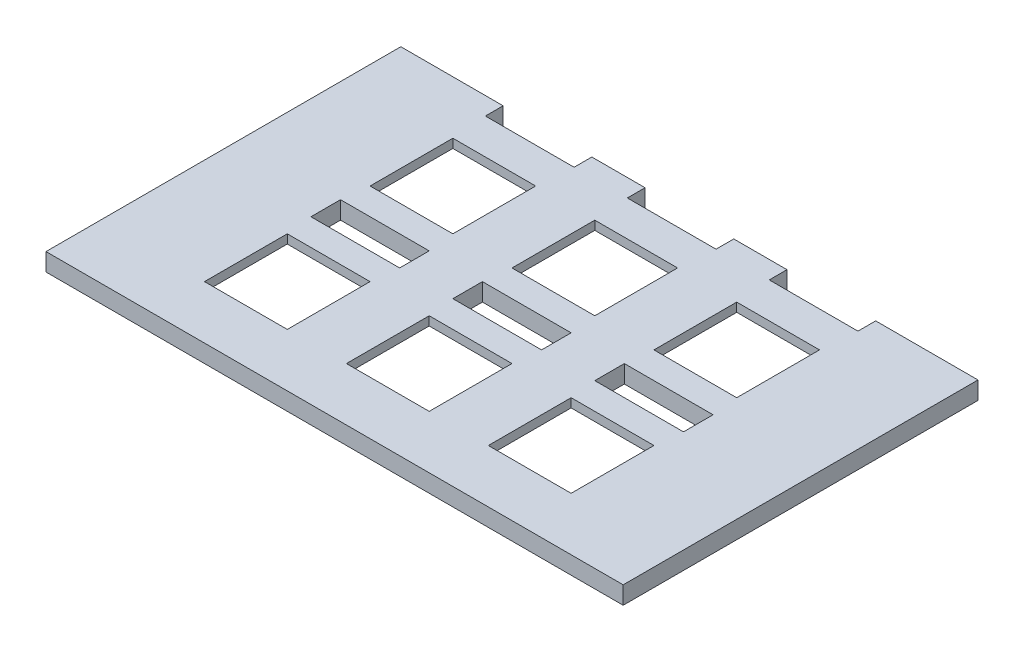
SolidWorks part; units mm, degrees
ref_plane "Front Plane" through (0, 0, 0) normal (0, 0, 1) x (1, 0, 0)
ref_plane "Top Plane" through (0, 0, 0) normal (0, 1, 0) x (1, 0, 0)
ref_plane "Right Plane" through (0, 0, 0) normal (1, 0, 0) x (0, 0, -1)
sketch "Sketch1" plane through (0, 0, 0) normal (0, 1, 0) x (1, 0, 0)
  line L1 (0, 0) -> (87.6, 0)
  line L2 (0, 0) -> (0, 60)
  line L3 (0, 60) -> (87.6, 60)
  line L4 (87.6, 0) -> (87.6, 60)
  dimension "D1" = 87.6
  dimension "D2" = 60
extrude "Boss-Extrude1" add sketch "Sketch1" along normal blind 3
sketch "Sketch2" plane through (87.6, 0, 0) normal (1, 0, 0) x (0, 0, -1)
  line L0 (0, 3) -> (60, 3) construction
  line L1 (2.3, 3) -> (57.7, 3)
  line L2 (2.3, 3) -> (2.3, 0)
  line L3 (2.3, 0) -> (57.7, 0)
  line L4 (57.7, 3) -> (57.7, 0)
  line L5 (0, 0) -> (60, 0) construction
  line L6 (0, 3) -> (0, 0) construction
  line L7 (60, 3) -> (60, 0) construction
  dimension "D1" = 2.3
  dimension "D2" = 2.3
extrude "Boss-Extrude2" add sketch "Sketch2" along normal blind 5
ref_plane "Plane1" through (43.8, 0, 0) normal (1, 0, 0) x (0, 0, -1)
mirror "Mirror2" about plane through (43.8, 0, 0) normal (1, 0, 0) of "Boss-Extrude2"
sketch "Sketch3" plane through (0, 0, 0) normal (0, -1, 0) x (1, 0, 0)
  line L0 (43.8, 0) -> (43.8, -60) construction
  line L1 (0, 0) -> (87.6, 0) construction
  line L2 (87.6, -60) -> (0, -60) construction
  line L3 (-5, -44) -> (90.6, -44) construction
  line L6 (43.8, -30) -> (51.1237, -30) construction
  line L7 (12.8, -51) -> (26.8, -51)
  line L8 (12.8, -51) -> (12.8, -37)
  line L9 (12.8, -37) -> (26.8, -37)
  line L10 (26.8, -51) -> (26.8, -37)
  line L11 (12.8, -51) -> (26.8, -37) construction
  line L12 (12.8, -37) -> (26.8, -51) construction
  line L13 (47.4618, -30) -> (47.4618, -60) construction
  line L14 (47.4618, -30) -> (47.4618, 0) construction
  line L15 (47.4618, -15) -> (43.8, -15) construction
  line L16 (47.4618, -45) -> (43.8, -45) construction
  point P12 (19.8, -44)
  dimension "D1" = 14
  dimension "D2" = 14
  dimension "D3" = 24
  dimension "D4" = 14
ref_plane "Plane2" through (0, 0, -30) normal (0, 0, -1) x (-1, 0, 0)
ref_axis "Axis1" through (43.8, -0.15, -30) along (0, 1, 0)
extrude "Cut-Extrude4" cut sketch "Sketch3" against normal through all
sketch "Sketch7" plane through (0, 0, 0) normal (0, -1, 0) x (1, 0, 0)
  line L0 (12.8, -44) -> (26.8, -44) construction
  line L1 (12.8, -37) -> (26.8, -37) construction
  line L2 (12.8, -37) -> (12.8, -51) construction
  line L3 (12.8, -51) -> (26.8, -51) construction
  line L4 (26.8, -37) -> (26.8, -51) construction
  line L5 (19.8, -37) -> (19.8, -51) construction
  line L7 (9.8, -54) -> (29.8, -54)
  line L8 (9.8, -54) -> (9.8, -34)
  line L9 (9.8, -34) -> (29.8, -34)
  line L10 (29.8, -54) -> (29.8, -34)
  line L11 (9.8, -54) -> (29.8, -34) construction
  line L12 (9.8, -34) -> (29.8, -54) construction
  point P10 (19.8, -44)
  dimension "D1" = 20
  dimension "D2" = 20
extrude "Cut-Extrude5" cut sketch "Sketch7" against normal offset from surface (1.5 mm away) 1.5 up to face at (19.8, 3, -44)
mirror "Mirror4" about plane through (43.8, 0, 0) normal (1, 0, 0) of "Cut-Extrude5", "Cut-Extrude4"
sketch "Sketch9" plane through (0, 0, -60) normal (0, 0, -1) x (-1, 0, 0)
  line L0 (-87.6, 3) -> (0, 3) construction
  line L1 (-12.3, 3) -> (-27.3, 3)
  line L2 (-12.3, 3) -> (-12.3, 0)
  line L3 (-12.3, 0) -> (-27.3, 0)
  line L4 (-27.3, 3) -> (-27.3, 0)
  line L5 (-87.6, 0) -> (0, 0) construction
  line L6 (-43.8, 3) -> (-43.8, 0) construction
  dimension "D1" = 15
  dimension "D2" = 16.5
extrude "Cut-Extrude6" cut sketch "Sketch9" against normal blind 3
mirror "Mirror6" about plane through (43.8, 0, 0) normal (1, 0, 0) of "Cut-Extrude6"
sketch "Sketch10" plane through (0, 3, 0) normal (0, 1, 0) x (1, 0, 0)
  line L0 (26.8, 51) -> (60.8, 51) construction
  line L1 (26.8, 37) -> (60.8, 37) construction
  line L3 (36.8, 51) -> (50.8, 51)
  line L4 (36.8, 51) -> (36.8, 37)
  line L5 (36.8, 37) -> (50.8, 37)
  line L6 (50.8, 51) -> (50.8, 37)
  point P12 (43.8, 51)
  point P13 (43.8, 51)
  dimension "D1" = 14
extrude "Cut-Extrude7" cut sketch "Sketch10" against normal blind 10
sketch "Sketch11" plane through (0, 0, 0) normal (0, -1, 0) x (1, 0, 0)
  line L0 (43.8, -37) -> (43.8, -51) construction
  line L1 (50.8, -37) -> (36.8, -37) construction
  line L2 (36.8, -51) -> (50.8, -51) construction
  line L4 (33.8, -34) -> (53.8, -34)
  line L5 (33.8, -34) -> (33.8, -54)
  line L6 (33.8, -54) -> (53.8, -54)
  line L7 (53.8, -34) -> (53.8, -54)
  line L8 (33.8, -34) -> (53.8, -54) construction
  line L9 (33.8, -54) -> (53.8, -34) construction
  point P6 (43.8, -44)
  dimension "D1" = 20
extrude "Cut-Extrude8" cut sketch "Sketch11" against normal blind 1.5
sketch "Sketch12" plane through (0, 0, 0) normal (0, -1, 0) x (1, 0, 0)
  line L0 (60.3, -60) -> (27.3, -60) construction
  line L1 (36.3, -60) -> (51.3, -60)
  line L2 (36.3, -60) -> (36.3, -57)
  line L3 (36.3, -57) -> (51.3, -57)
  line L4 (51.3, -60) -> (51.3, -57)
  line L5 (60.3, -57) -> (75.3, -57) construction
  line L6 (43.8, -60) -> (43.8, -51) construction
  line L7 (50.8, -51) -> (36.8, -51) construction
  dimension "D1" = 15
extrude "Cut-Extrude9" cut sketch "Sketch12" against normal blind 40
ref_plane "Plane3" through (0, 0, -30) normal (0, 0, 1) x (1, 0, 0)
mirror "Mirror8" about plane through (0, 0, -30) normal (0, 0, 1) of "Cut-Extrude5", "Mirror4", "Cut-Extrude7", "Cut-Extrude8"
sketch "Sketch13" plane through (0, 3, 0) normal (0, 1, 0) x (1, 0, 0)
  line L0 (92.6, 57.7) -> (92.6, 2.3) construction
  line L1 (0, 57.7) -> (-5, 57.7)
  line L2 (0, 57.7) -> (0, 60)
  line L3 (0, 60) -> (-5, 60)
  line L4 (-5, 57.7) -> (-5, 60)
  line L5 (0, 2.3) -> (-5, 2.3)
  line L6 (0, 2.3) -> (0, 0)
  line L7 (0, 0) -> (-5, 0)
  line L8 (-5, 2.3) -> (-5, 0)
  line L9 (87.6, 2.3) -> (92.6, 2.3)
  line L10 (87.6, 2.3) -> (87.6, 0)
  line L11 (87.6, 0) -> (92.6, 0)
  line L12 (92.6, 2.3) -> (92.6, 0)
  line L14 (87.6, 57.7) -> (92.6, 57.7)
  line L15 (87.6, 57.7) -> (87.6, 60)
  line L16 (87.6, 60) -> (92.6, 60)
  line L17 (92.6, 57.7) -> (92.6, 60)
extrude "Boss-Extrude3" add sketch "Sketch13" against normal up to surface (3 mm away) up to face at (19.8, 0, -16)
sketch "Sketch15" plane through (0, 0, 0) normal (0, -1, 0) x (1, 0, 0)
  line L0 (19.8, -34) -> (19.8, -26) construction
  line L1 (9.8, -34) -> (29.8, -34) construction
  line L2 (29.8, -26) -> (9.8, -26) construction
  line L3 (19.8, -31.5) -> (83.6104, -31.5) construction
  line L8 (9.8, -26) -> (29.8, -26) construction
  line L9 (12.3, -27.5) -> (27.3, -27.5)
  line L10 (12.3, -27.5) -> (12.3, -32.5)
  line L11 (12.3, -32.5) -> (27.3, -32.5)
  line L12 (27.3, -27.5) -> (27.3, -32.5)
  line L13 (36.3, -27.5) -> (36.3, -32.5)
  line L14 (36.3, -27.5) -> (51.3, -27.5)
  line L15 (51.3, -27.5) -> (51.3, -32.5)
  line L16 (36.3, -32.5) -> (51.3, -32.5)
  line L17 (43.8, -31.5) -> (107.6104, -31.5) construction
  line L18 (60.3, -27.5) -> (60.3, -32.5)
  line L19 (60.3, -27.5) -> (75.3, -27.5)
  line L20 (75.3, -27.5) -> (75.3, -32.5)
  line L21 (60.3, -32.5) -> (75.3, -32.5)
  line L22 (67.8, -31.5) -> (131.6104, -31.5) construction
  point P10 (19.8, -27.5)
  dimension "D1" = 15
  dimension "D2" = 5
  dimension "D3" = 1.5
  dimension "D4" = 3
extrude "Cut-Extrude11" cut sketch "Sketch15" against normal through all
